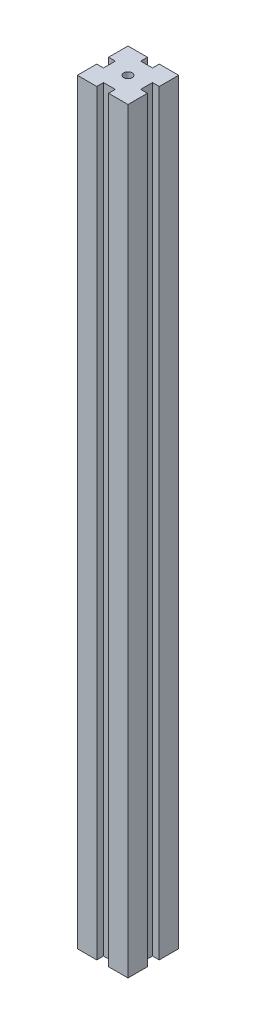
SolidWorks part; units mm, degrees
ref_plane "Front Plane" through (0, 0, 0) normal (0, 0, 1) x (1, 0, 0)
ref_plane "Top Plane" through (0, 0, 0) normal (0, 1, 0) x (1, 0, 0)
ref_plane "Right Plane" through (0, 0, 0) normal (1, 0, 0) x (0, 0, -1)
sketch "Sketch1" plane through (0, 0, 0) normal (0, 1, 0) x (1, 0, 0)
  line L0 (7.5, 15) -> (7.5, 0) construction
  line L1 (0, 0) -> (15, 0)
  line L2 (0, 0) -> (0, 15)
  line L3 (0, 15) -> (15, 15)
  line L4 (15, 0) -> (15, 15)
  line L5 (5.75, 0) -> (9.25, 0)
  line L6 (5.75, 0) -> (5.75, 2)
  line L7 (5.75, 2) -> (9.25, 2)
  line L8 (9.25, 0) -> (9.25, 2)
  line L9 (5.75, 15) -> (9.25, 15)
  line L10 (5.75, 15) -> (5.75, 13)
  line L11 (5.75, 13) -> (9.25, 13)
  line L12 (9.25, 15) -> (9.25, 13)
  line L13 (15, 9.25) -> (13, 9.25)
  line L14 (15, 9.25) -> (15, 5.75)
  line L15 (15, 5.75) -> (13, 5.75)
  line L16 (13, 9.25) -> (13, 5.75)
  line L17 (0, 9.25) -> (2, 9.25)
  line L18 (0, 9.25) -> (0, 5.75)
  line L19 (0, 5.75) -> (2, 5.75)
  line L20 (2, 9.25) -> (2, 5.75)
  line L21 (0, 7.5) -> (15, 7.5) construction
  point P25 (0, 0)
  point P26 (-40.0521, 18.4535)
  point P27 (-4.5092, 9.5645)
  point P28 (-3.6353, 8.9492)
  point P29 (-3.9292, 6.8227)
  dimension "D1" = 15
  dimension "D2" = 2
  dimension "15" = 15
  dimension "D3" = 2
  dimension "D4" = 3.5
  dimension "D5" = 3.5
extrude "Boss-Extrude1" add sketch "Sketch1" along normal blind 224 contours L17 L20 L19 L2 L1 L6 L7 L8 L4 L15 L16 L13 L3 L12 L11 L10 region at (7.5, 0, -7.5)
sketch "Sketch2" plane through (0, 224, 0) normal (0, 1, 0) x (1, 0, 0)
  line L0 (0, 15) -> (15, 0) construction
  circle A0 centre (7.5, 7.5) radius 1.25
  dimension "D1" = 2.5
extrude "Cut-Extrude1" cut sketch "Sketch2" against normal through all
